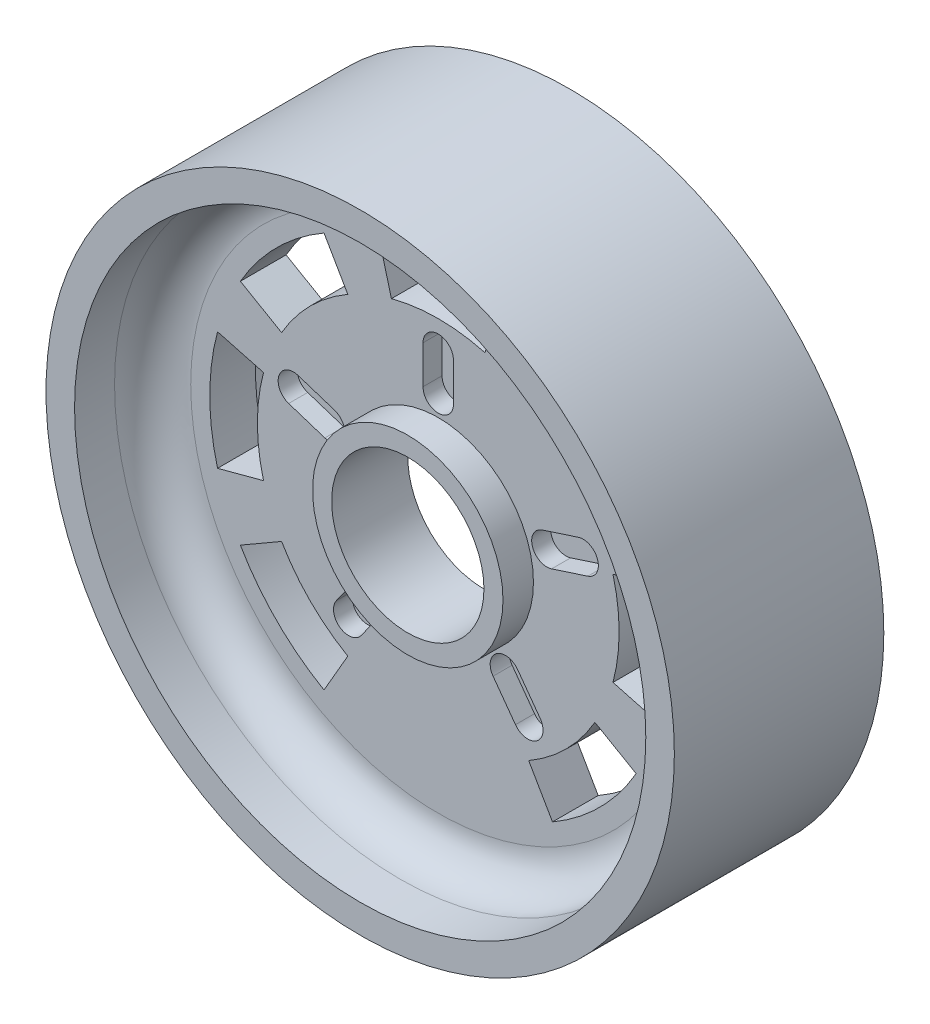
SolidWorks part; units mm, degrees
material "Cast Stainless Steel"
ref_plane "Front Plane" through (0, 0, 0) normal (0, 0, 1) x (1, 0, 0)
ref_plane "Top Plane" through (0, 0, 0) normal (0, 1, 0) x (1, 0, 0)
ref_plane "Right Plane" through (0, 0, 0) normal (1, 0, 0) x (0, 0, -1)
sketch "Sketch1" plane through (0, 0, 0) normal (1, 0, 0) x (0, 0, -1)
  line L0 (0, 0) -> (20.1399, 0) construction
  line L1 (0, 12.7) -> (0, 10.16)
  line L2 (0, 10.16) -> (10.16, 10.16)
  line L3 (10.16, 10.16) -> (10.16, 35.052)
  line L4 (10.16, 35.052) -> (21.59, 38.1)
  line L5 (21.59, 38.1) -> (21.59, 41.91)
  line L6 (21.59, 41.91) -> (-6.35, 41.91)
  line L7 (-6.35, 41.91) -> (-6.35, 38.1)
  line L8 (-6.35, 38.1) -> (-1.016, 38.1)
  line L9 (4.064, 33.02) -> (4.064, 12.7)
  line L10 (4.064, 12.7) -> (0, 12.7)
  arc A0 (-1.016, 38.1) -> (4.064, 33.02) centre (-1.016, 33.02) cw
  point P15 (4.064, 38.1)
  dimension "D11" = 5.08
  dimension "D1" = 10.16
  dimension "D2" = 3.048
  dimension "D3" = 3.81
  dimension "D4" = 3.81
  dimension "D5" = 2.54
  dimension "D6" = 4.064
  dimension "D7" = 11.43
  dimension "D8" = 27.94
  dimension "D9" = 25.4
  dimension "D10" = 10.16
revolve "Revolve1" add sketch "Sketch1" angle 360 about L0
sketch "Sketch2" plane through (0, 0, -4.064) normal (0, 0, 1) x (1, 0, 0)
  line L0 (0, 0) -> (0, 46.2936) construction
  line L1 (12.7217, 47.4782) -> (7.8888, 29.4414) construction
  line L2 (0, 0) -> (-6.2453, 23.3078) construction
  line L3 (-7.8888, 29.4414) -> (-14.215, 53.0511) construction
  line L4 (6.2453, 23.3078) -> (0, 0) construction
  line L5 (-7.8888, 29.4414) -> (-6.2453, 23.3078)
  line L6 (6.2453, 23.3078) -> (7.8888, 29.4414)
  line L7 (0, 20.32) -> (0, 15.24) construction
  line L8 (2.032, 20.32) -> (2.032, 15.24)
  line L9 (-2.032, 20.32) -> (-2.032, 15.24)
  arc A0 (6.2453, 23.3078) -> (-6.2453, 23.3078) centre (0, 0) ccw
  arc A1 (7.8888, 29.4414) -> (-7.8888, 29.4414) centre (0, 0) ccw
  arc A2 (2.032, 20.32) -> (-2.032, 20.32) centre (0, 20.32) ccw
  arc A3 (-2.032, 15.24) -> (2.032, 15.24) centre (0, 15.24) ccw
  point P12 (0, 17.78)
  point P17 (0, 0)
  point P18 (0, 0)
  point P19 (0, 0)
  point P20 (0, 0)
  point P21 (0, 0)
  point P22 (0, 0)
  point P23 (0, 0)
  point P24 (0, 0)
  point P25 (0, 0)
  dimension "D3" = 48.26
  dimension "D4" = 60.96
  dimension "D6" = 2.032
  dimension "D1" = 15
  dimension "D2" = 15
  dimension "D5" = 5.08
  dimension "D7" = 17.78
extrude "Cut-Extrude5" cut sketch "Sketch2" against normal through all contours A0 L5 A1 L6
extrude "Cut-Extrude6" cut sketch "Sketch2<9>" against normal blind 2.54 contours L8 A3 L9 A2
sketch "Sketch2<9>" plane through (0, 0, -4.064) normal (0, 0, 1) x (1, 0, 0) same geometry as "Sketch2"
pattern_circular "CirPattern1" count 5 over 360 about axis through (0, 0, 0) along (0, 0, 1) of "Cut-Extrude6"
pattern_circular "CirPattern2" count 8 over 360 about axis through (0, 0, 0) along (0, 0, 1) skipping 4 of "Cut-Extrude5"
